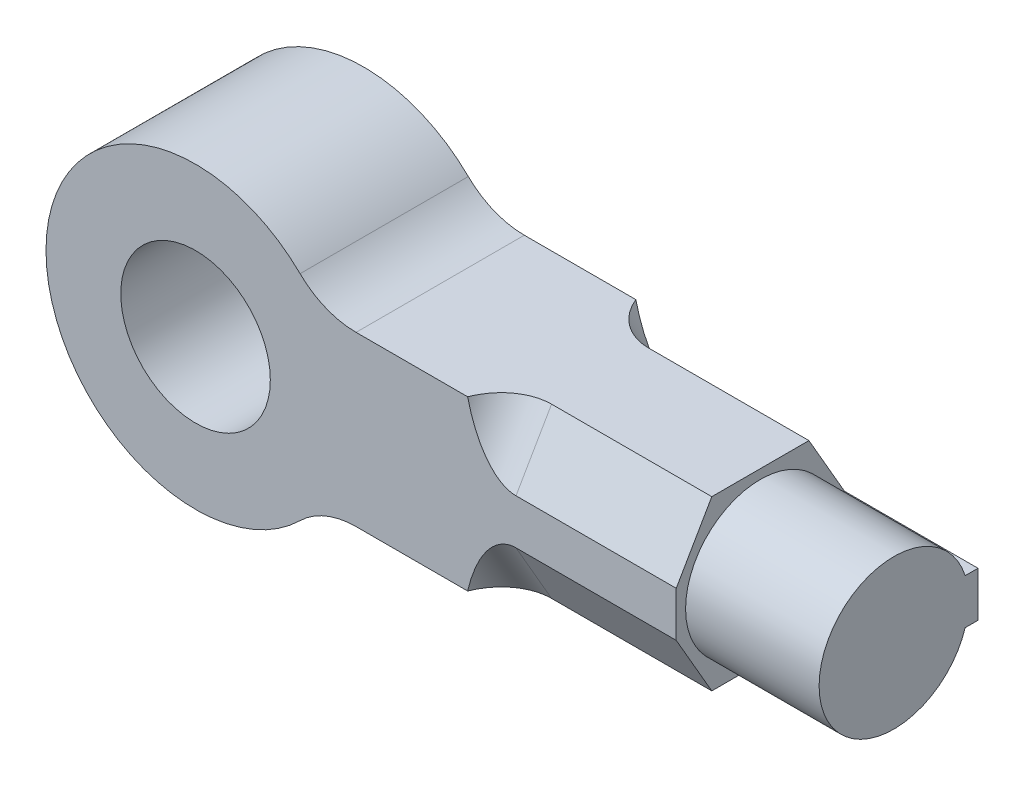
SolidWorks part; units mm, degrees
ref_plane "Front Plane" through (0, 0, 0) normal (0, 0, 1) x (1, 0, 0)
ref_plane "Top Plane" through (0, 0, 0) normal (0, 1, 0) x (1, 0, 0)
ref_plane "Right Plane" through (0, 0, 0) normal (1, 0, 0) x (0, 0, -1)
sketch "Sketch1" plane through (0, 0, 0) normal (0, 0, 1) x (1, 0, 0)
  circle A0 centre (0, 0) radius 28
  circle A1 centre (0, 0) radius 56
  dimension "D1" = 56
  dimension "D2" = 112
extrude "Boss-Extrude1" add sketch "Sketch1" along normal mid plane 63
ref_plane "Plane1" through (180, 0, 0) normal (1, 0, 0) x (0, 0, -1)
sketch "Sketch2" plane through (180, 0, 0) normal (1, 0, 0) x (0, 0, -1)
  line L0 (-31.5, 56) -> (-31.5, -56) construction
  line L1 (31.5, -31.5) -> (-31.5, -31.5)
  line L2 (31.5, -31.5) -> (31.5, 31.5)
  line L3 (31.5, 31.5) -> (-31.5, 31.5)
  line L4 (-31.5, -31.5) -> (-31.5, 31.5)
  line L5 (31.5, -31.5) -> (-31.5, 31.5) construction
  line L6 (31.5, 31.5) -> (-31.5, -31.5) construction
  point P0 (0, 0)
  dimension "D1" = 63
extrude "Boss-Extrude2" add sketch "Sketch2" against normal up to next
fillet "Fillet1" radius 30 2 edges at (46.3006, -31.5, 0) (46.3006, 31.5, 0)
sketch "Sketch3" plane through (180, 0, 0) normal (1, 0, 0) x (0, 0, -1)
  circle A0 centre (0, 0) radius 28
  dimension "D1" = 56
extrude "Boss-Extrude3" add sketch "Sketch3" along normal blind 50
sketch "Sketch4" plane through (180, 0, 0) normal (1, 0, 0) x (0, 0, -1)
  line L1 (18.1865, -31.5) -> (36.3731, 0)
  line L2 (36.3731, 0) -> (18.1865, 31.5)
  line L3 (18.1865, 31.5) -> (-18.1865, 31.5)
  line L4 (-18.1865, 31.5) -> (-36.3731, 0)
  line L5 (-36.3731, 0) -> (-18.1865, -31.5)
  line L6 (-18.1865, -31.5) -> (18.1865, -31.5)
  circle A0 centre (0, 0) radius 31.5 construction
  circle A1 centre (0, 0) radius 53.4405
extrude "Cut-Extrude1" cut sketch "Sketch4" against normal blind 80
fillet "Fillet2" radius 20 4 edges at (100, 19.9702, 24.8433) (100, -19.9702, 24.8433) (100, -19.9702, -24.8433) (100, 19.9702, -24.8433)
sketch "Sketch5" plane through (180, 0, 0) normal (1, 0, 0) x (0, 0, -1)
  line L0 (31.5, 8.4404) -> (26.6976, 8.4404)
  line L1 (31.5, 8.4404) -> (31.5, -8.4404)
  line L2 (31.5, -8.4404) -> (26.6976, -8.4404)
  circle A0 centre (0, 0) radius 28 construction
  arc A1 (26.6976, -8.4404) -> (26.6976, 8.4404) centre (0, 0) ccw
extrude "Boss-Extrude4" add sketch "Sketch5" along normal up to surface (50 mm away) up to face at (230, 0, -28)
sketch "Sketch6" plane through (0, 0, 0) normal (0, 0, 1) x (1, 0, 0)
  arc A0 (97.5836, 214.8801) -> (101.8822, -212.8756) centre (0, 0) ccw
